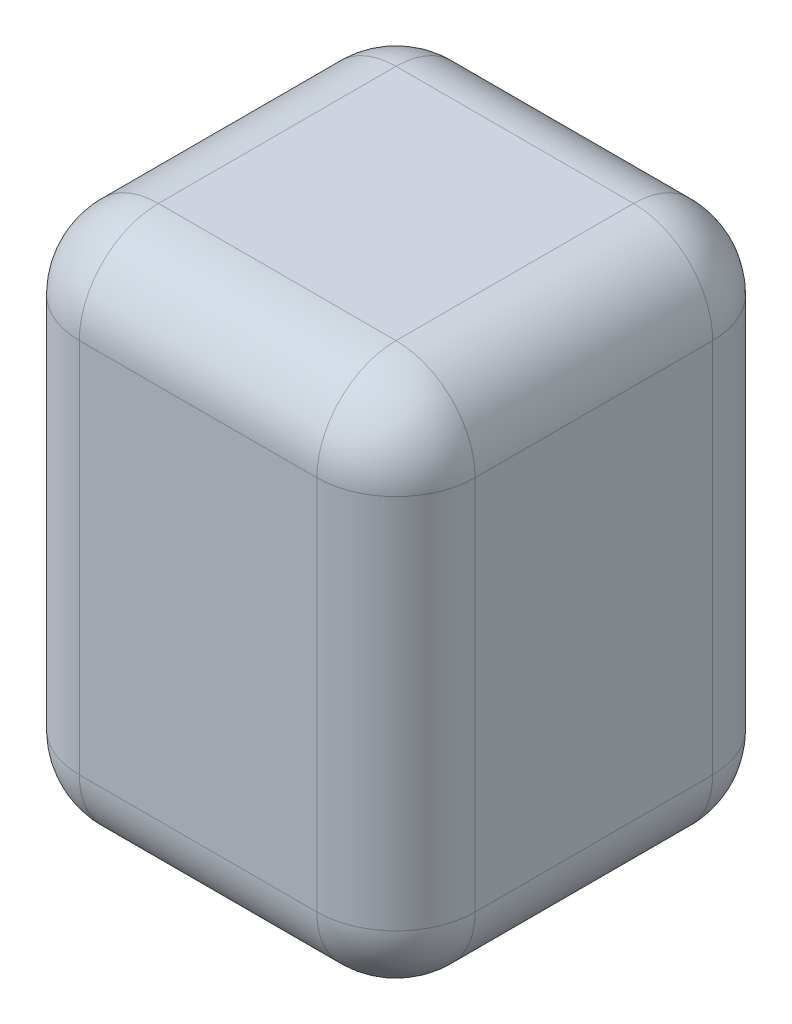
SolidWorks part; units mm, degrees
ref_plane "Front Plane" through (0, 0, 0) normal (0, 0, 1) x (1, 0, 0)
ref_plane "Top Plane" through (0, 0, 0) normal (0, 1, 0) x (1, 0, 0)
ref_plane "Right Plane" through (0, 0, 0) normal (1, 0, 0) x (0, 0, -1)
sketch "Sketch1" plane through (0, 0, 0) normal (0, 1, 0) x (1, 0, 0)
  line L0 (0, 50) -> (0, -50) construction
  line L1 (-50, 50) -> (50, 50)
  line L2 (-50, 50) -> (-50, -50)
  line L3 (-50, -50) -> (50, -50)
  line L4 (50, 50) -> (50, -50)
  line L5 (-50, 0) -> (50, 0) construction
  dimension "D1" = 100
  dimension "D2" = 100
extrude "Boss-Extrude1" add sketch "Sketch1" along normal blind 135
fillet "Fillet1" radius 20 12 edges at (0, 0, -50) (50, 67.5, -50) (50, 0, 0) (-50, 67.5, -50) (-50, 0, 0) (-50, 67.5, 50) (50, 67.5, 50) (0, 0, 50) (0, 135, -50) (50, 135, 0) (0, 135, 50) (-50, 135, 0)
shell "Shell1" thickness 1.5
